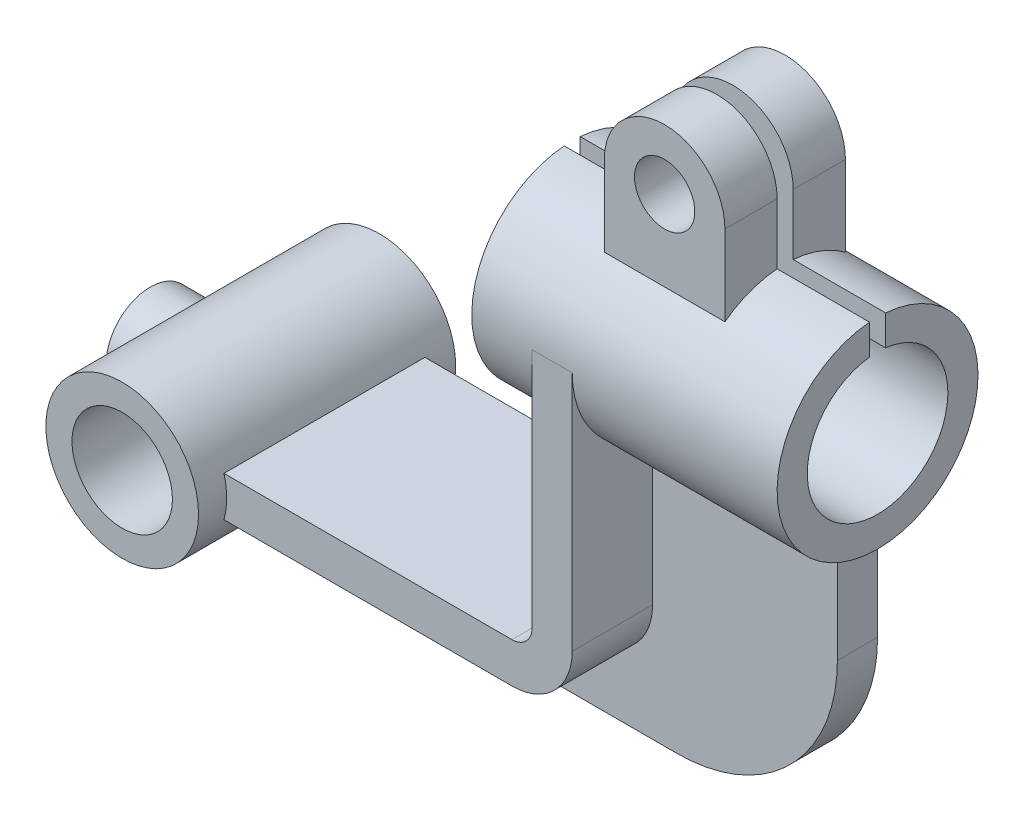
SolidWorks part; units mm, degrees
ref_plane "前视基准面" through (0, 0, 0) normal (0, 0, 1) x (1, 0, 0)
ref_plane "上视基准面" through (0, 0, 0) normal (0, 1, 0) x (1, 0, 0)
ref_plane "右视基准面" through (0, 0, 0) normal (1, 0, 0) x (0, 0, -1)
other "Configuration Table"
sketch "草图2" plane through (0, 0, 0) normal (1, 0, 0) x (0, 0, -1)
  circle A0 centre (0, 70) radius 25
  circle A1 centre (0, 70) radius 17.5
  dimension "D1" = 35
  dimension "D2" = 50
  dimension "D3" = 0
  dimension "D4" = 70
extrude "凸台-拉伸1" add sketch "草图2" along normal mid plane 76
sketch "草图3" plane through (0, 0, 0) normal (0, 0, 1) x (1, 0, 0)
  line L0 (0, 157.0033) -> (0, -17.1002) construction
  line L1 (-15, 110) -> (-15, 87.5)
  line L2 (-15, 87.5) -> (15, 87.5)
  line L3 (15, 87.5) -> (15, 110)
  line L4 (38, 87.5) -> (-38, 87.5) construction
  line L6 (38, 70) -> (-38, 70) construction
  circle A0 centre (0, 110) radius 7.5
  arc A1 (15, 110) -> (-15, 110) centre (0, 110) ccw
  dimension "D1" = 15
  dimension "D2" = 30
  dimension "D3" = 40
extrude "凸台-拉伸2" add sketch "草图3" along normal mid plane 30
sketch "草图4" plane through (0, 0, 0) normal (0, 1, 0) x (1, 0, 0)
  line L0 (38, -25) -> (38, 25) construction
  line L1 (-38, 2) -> (38, 2)
  line L2 (-38, 2) -> (-38, -2)
  line L3 (-38, -2) -> (38, -2)
  line L4 (38, 2) -> (38, -2)
  line L5 (-38, 2) -> (38, -2) construction
  line L6 (-38, -2) -> (38, 2) construction
  point P0 (0, 0)
  dimension "D1" = 4
extrude "切除-拉伸1" cut sketch "草图4" along normal through all from offset 70
sketch "草图5" plane through (0, 0, 0) normal (0, 0, 1) x (1, 0, 0)
  line L3 (-118, -19) -> (-7, -19)
  line L4 (33, 21) -> (33, 70)
  line L5 (38, 45) -> (38, 94.9199) construction
  line L6 (-38, 94.9199) -> (-38, 45) construction
  line L7 (38, 70) -> (-38, 70) construction
  line L8 (-13, 70) -> (-13, 10)
  line L9 (-28, -5) -> (-99.6697, -5)
  line L10 (-23, 70) -> (-23, 10)
  line L11 (-28, 5) -> (-99.6697, 5)
  line L12 (-23, 45) -> (-23, 10) construction
  line L14 (-13, 45) -> (-13, 10) construction
  line L15 (-23, 70) -> (33, 70)
  line L16 (38, 70) -> (15, 70) construction
  arc A0 (-7, -19) -> (33, 21) centre (-7, 21) ccw
  circle A1 centre (-118, 0) radius 19
  circle A2 centre (-118, 0) radius 12.5
  arc A3 (-13, 10) -> (-28, -5) centre (-28, 10) cw
  arc A4 (-23, 10) -> (-28, 5) centre (-28, 10) cw
  dimension "D2" = 40
  dimension "D6" = 38
  dimension "D7" = 15
  dimension "D4" = 25
  dimension "D1" = 5
  dimension "D3" = 80
  dimension "D5" = 70
  dimension "D9" = 15
  dimension "D8" = 10
extrude "凸台-拉伸3" add sketch "草图5" along normal mid plane 50 contours L10 A4 L11 A1 L9 A3 L8 L15 region at (-63.8348, 3.8538, 0)
extrude "凸台-拉伸4" add sketch "草图5<5>" along normal mid plane 10 contours L8 A3 L9 A1 L3 A0 L4 L15 region at (-8.5495, 18.1495, 0)
sketch "草图5<5>" plane through (0, 0, 0) normal (0, 0, 1) x (1, 0, 0) same geometry as "草图5"
extrude "凸台-拉伸5" add sketch "草图5<6>" along normal mid plane 64 contours A1 A2 region at (-132.6726, 11.2064, 0)
sketch "草图5<6>" plane through (0, 0, 0) normal (0, 0, 1) x (1, 0, 0) same geometry as "草图5"
ref_plane "基准面1" through (-143, 0, 0) normal (-1, 0, 0) x (0, 0, 1)
sketch "草图7" plane through (-143, 0, 0) normal (-1, 0, 0) x (0, 0, 1)
  circle A0 centre (0, 0) radius 11
  circle A1 centre (0, 0) radius 7.5
  dimension "D1" = 15
  dimension "D2" = 22
extrude "凸台-拉伸6" add sketch "草图7" against normal up to next
extrude "切除-拉伸2" cut sketch "草图7<2>" against normal up to next contours A1 region at (-143, 0, 0)
sketch "草图7<2>" plane through (-143, 0, 0) normal (-1, 0, 0) x (0, 0, 1) same geometry as "草图7"
sketch "草图8" plane through (0, 0, 0) normal (1, 0, 0) x (0, 0, -1)
  circle A0 centre (0, 70) radius 17.5
  dimension "D1" = 35
extrude "切除-拉伸3" cut sketch "草图8" against normal up to next and the other way through all
